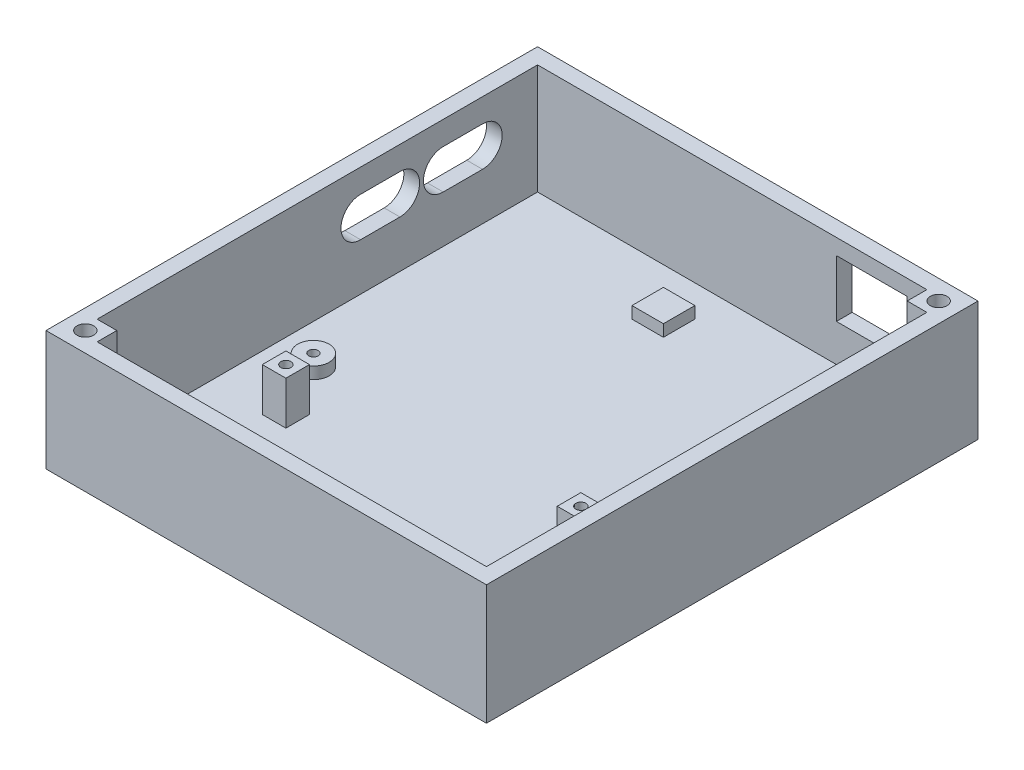
SolidWorks part; units mm, degrees
ref_plane "Front Plane" through (0, 0, 0) normal (0, 0, 1) x (1, 0, 0)
ref_plane "Top Plane" through (0, 0, 0) normal (0, 1, 0) x (1, 0, 0)
ref_plane "Right Plane" through (0, 0, 0) normal (1, 0, 0) x (0, 0, -1)
sketch "Sketch1" plane through (0, 0, 0) normal (0, 1, 0) x (1, 0, 0)
  line L1 (-56, -62.5) -> (56, -62.5)
  line L2 (-56, -62.5) -> (-56, 62.5)
  line L3 (-56, 62.5) -> (56, 62.5)
  line L4 (56, -62.5) -> (56, 62.5)
  line L5 (-56, -62.5) -> (56, 62.5) construction
  line L6 (-56, 62.5) -> (56, -62.5) construction
  point P0 (0, 0)
  dimension "D1" = 112
  dimension "D2" = 125
extrude "Boss-Extrude1" add sketch "Sketch1" along normal blind 2.5
sketch "Sketch2" plane through (0, 2.5, 0) normal (0, 1, 0) x (1, 0, 0)
  line L0 (-56, -62.5) -> (56, -62.5) construction
  line L1 (-12, 50.5) -> (-4, 50.5) construction
  line L2 (-12, 50.5) -> (-12, 42.5) construction
  line L3 (-12, 42.5) -> (-4, 42.5) construction
  line L4 (52, 53.5) -> (47, 53.5)
  line L5 (-4, 50.5) -> (-4, 42.5) construction
  line L6 (-56, 62.5) -> (-56, -62.5) construction
  line L7 (47, 53.5) -> (47, 58.5)
  line L8 (52, -58.5) -> (52, 58.5)
  line L9 (52, 58.5) -> (-52, 58.5)
  line L10 (-52, 58.5) -> (-52, -58.5)
  line L11 (-52, -58.5) -> (52, -58.5)
  line L12 (52, -58.5) -> (52, 53.5)
  line L13 (47, 58.5) -> (-52, 58.5)
  line L14 (-52, 58.5) -> (-52, -53.5)
  line L15 (-47, -58.5) -> (52, -58.5)
  line L16 (56, 62.5) -> (-56, 62.5) construction
  line L29 (-47, -58.5) -> (-47, -53.5)
  line L30 (-47, -53.5) -> (-52, -53.5)
  line L31 (56, -62.5) -> (56, 62.5) construction
  circle A0 centre (-42, -8.5) radius 1.2 construction
  circle A1 centre (38, -8.5) radius 1.2 construction
  circle A2 centre (-51, -57.5) radius 2.1
  circle A3 centre (51, 57.5) radius 2.1
  line M12 (56, -62.5) -> (56, 62.5)
  line M13 (56, 62.5) -> (-56, 62.5)
  line M14 (-56, 62.5) -> (-56, -62.5)
  line M15 (-56, -62.5) -> (56, -62.5)
  dimension "D1" = 2.4
  dimension "D13" = 4.2
  dimension "D15" = 4.2
  dimension "D18" = 5
  dimension "D2" = 80
  dimension "D3" = 5
  dimension "D5" = 8
  dimension "D6" = 62
  dimension "D7" = 5
  dimension "D8" = 14
  dimension "D9" = 8
  dimension "D10" = 8
  dimension "D11" = 40
  dimension "D12" = 5
  dimension "D14" = 5
  dimension "D16" = 5
  dimension "D17" = 5
  dimension "D4" = 4
extrude "Boss-Extrude2" add sketch "Sketch2" along normal blind 10 contours A0 | A1 | A3 A2 L29 L30 L14 L13 L7 L4 L12 L15 M15 M12 M13 M14 region at (48.9478, 2.5, -55.4478) region at (-48.9478, 2.5, 55.4478) region at (0, 2.5, 60.8216)
sketch "Sketch3" plane through (0, 2.5, 0) normal (0, 1, 0) x (1, 0, 0)
  line L0 (-32, -50.5) -> (-32, -25.5) construction
  line L1 (-35, -53.5) -> (40, -53.5) construction
  line L2 (-35, -53.5) -> (-35, -22.5) construction
  line L3 (-35, -22.5) -> (40, -22.5) construction
  line L4 (40, -53.5) -> (40, -22.5) construction
  line L5 (-32, -25.5) -> (37, -25.5) construction
  line L6 (37, -50.5) -> (37, -25.5) construction
  line L7 (-32, -50.5) -> (37, -50.5) construction
  line L8 (-38, -19.5) -> (43, -19.5)
  line L9 (43, -56.5) -> (43, -19.5)
  line L10 (-38, -56.5) -> (43, -56.5)
  line L11 (-38, -56.5) -> (-38, -19.5)
  line L12 (-47, -58.5) -> (52, -58.5) construction
  line L13 (-47, -58.5) -> (52, -58.5) construction
  line L14 (-32, -25.5) -> (-38, -25.5)
  line L15 (-32, -50.5) -> (-38, -50.5)
  line L16 (37, -25.5) -> (43, -25.5)
  line L17 (37, -50.5) -> (43, -50.5)
  line L18 (37, -25.5) -> (37, -19.5)
  line L19 (37, -50.5) -> (37, -56.5)
  line L20 (-32, -50.5) -> (-32, -56.5)
  line L21 (-32, -19.5) -> (-32, -25.5)
  circle A0 centre (-35, -22.5) radius 1.3
  circle A1 centre (40, -22.5) radius 1.3
  circle A2 centre (40, -53.5) radius 1.3
  circle A3 centre (-35, -53.5) radius 1.3
  point P17 (2.5, -22.5)
  point P19 (2.5, -58.5)
  dimension "D3" = 2.6
  dimension "D4" = 75
  dimension "D5" = 31
  dimension "D6" = 5
  dimension "D1" = 3
  dimension "D2" = 3
extrude "Boss-Extrude3" add sketch "Sketch3" along normal blind 11 contours L20 L15 L11 L10 A3 | L21 L8 L11 L14 A0 | L18 L16 L9 L8 A1 | L17 L19 L10 L9 A2 region at (-35, 2.5, 19.5849) region at (40, 2.5, 19.5849) region at (-35, 2.5, 50.5849) region at (42.9151, 2.5, 53.5)
sketch "Sketch5" plane through (0, 2.5, 0) normal (0, 1, 0) x (1, 0, 0)
  line L0 (-4, 50.5) -> (-4, 42.5) construction
  line L1 (-12, 50.5) -> (-4, 50.5) construction
  line L2 (-12, 50.5) -> (-12, 42.5) construction
  line L3 (-12, 42.5) -> (-4, 42.5) construction
  line L4 (-4, 50.5) -> (-4, 42.5)
  line L5 (-12, 50.5) -> (-4, 50.5)
  line L6 (-12, 50.5) -> (-12, 42.5)
  line L7 (-12, 42.5) -> (-4, 42.5)
  circle A0 centre (-42, -8.5) radius 4
  circle A1 centre (38, -8.5) radius 4
  circle A2 centre (38, -8.5) radius 1.2 construction
  circle A3 centre (38, -8.5) radius 1.2
  circle A4 centre (-42, -8.5) radius 1.2 construction
  circle A5 centre (-42, -8.5) radius 1.2
  dimension "D1" = 8
extrude "Boss-Extrude4" add sketch "Sketch5" along normal blind 3
sketch "Sketch6" plane through (0, 13.5, 0) normal (0, 1, 0) x (1, 0, 0)
  line L4 (-32, -56.5) -> (-32, -50.5)
  line L5 (-32, -50.5) -> (-38, -50.5)
  line L6 (-38, -50.5) -> (-38, -56.5)
  line L7 (-38, -56.5) -> (-32, -56.5)
  line L8 (-32, -56.5) -> (-32, -50.5)
  line L9 (-32, -50.5) -> (-38, -50.5)
  line L10 (-38, -50.5) -> (-38, -56.5)
  line L11 (-38, -56.5) -> (-32, -56.5)
  line L12 (37, -19.5) -> (37, -25.5)
  line L13 (37, -25.5) -> (43, -25.5)
  line L14 (43, -25.5) -> (43, -19.5)
  line L15 (43, -19.5) -> (37, -19.5)
  line L16 (37, -19.5) -> (37, -25.5)
  line L17 (37, -25.5) -> (43, -25.5)
  line L18 (43, -25.5) -> (43, -19.5)
  line L19 (43, -19.5) -> (37, -19.5)
  line L20 (43, -50.5) -> (37, -50.5)
  line L21 (37, -50.5) -> (37, -56.5)
  line L22 (37, -56.5) -> (43, -56.5)
  line L23 (43, -56.5) -> (43, -50.5)
  line L24 (43, -50.5) -> (37, -50.5)
  line L25 (37, -50.5) -> (37, -56.5)
  line L26 (37, -56.5) -> (43, -56.5)
  line L27 (43, -56.5) -> (43, -50.5)
  circle A0 centre (40, -53.5) radius 1.3 construction
  circle A1 centre (40, -22.5) radius 1.3
  circle A2 centre (40, -22.5) radius 1.3
  circle A3 centre (-35, -53.5) radius 1.3 construction
  circle A4 centre (40, -53.5) radius 1.3
  circle A5 centre (-35, -53.5) radius 1.3
  dimension "D1" = 0
  dimension "D2" = 0
  dimension "D3" = 0
  dimension "D4" = 0
extrude "Boss-Extrude5" add sketch "Sketch6" along normal blind 6.3
sketch "Sketch7" plane through (0, 12.5, 0) normal (0, 1, 0) x (1, 0, 0)
  line L4 (-56, -62.5) -> (56, -62.5)
  line L5 (56, -62.5) -> (56, 62.5)
  line L6 (56, 62.5) -> (-56, 62.5)
  line L7 (-56, 62.5) -> (-56, -62.5)
  line L8 (-56, -62.5) -> (56, -62.5)
  line L9 (56, -62.5) -> (56, 62.5)
  line L10 (56, 62.5) -> (-56, 62.5)
  line L11 (-56, 62.5) -> (-56, -62.5)
  circle M5 centre (51, 57.5) radius 2.1
  line M6 (47, 53.5) -> (52, 53.5)
  line M7 (52, 53.5) -> (52, -58.5)
  line M13 (52, 53.5) -> (52, -58.5)
  line M14 (52, -58.5) -> (-47, -58.5)
  line M15 (-47, -58.5) -> (-47, -53.5)
  line M16 (-47, -53.5) -> (-52, -53.5)
  line M17 (-52, -53.5) -> (-52, 58.5)
  line M18 (-52, 58.5) -> (47, 58.5)
  line M19 (47, 58.5) -> (47, 53.5)
  circle M22 centre (-51, -57.5) radius 2.1
  line M23 (-56, -62.5) -> (56, -62.5)
  line M24 (56, -62.5) -> (56, 62.5)
  line M25 (56, 62.5) -> (-56, 62.5)
  line M26 (-56, 62.5) -> (-56, -62.5)
  dimension "D1" = 0
extrude "Boss-Extrude6" add sketch "Sketch7" along normal blind 18 contours M26 M23 M24 M25 M22 M5 M7 M13 M14 M15 M16 M17 M18 M19 M6 region at (-54.3216, 12.5, 0)
sketch "Sketch9" plane through (-56, 0, 0) normal (-1, 0, 0) x (0, 0, 1)
  line L0 (-44.5, 19.5) -> (-34.5, 19.5) construction
  line L1 (-44.5, 24.5) -> (-34.5, 24.5)
  line L2 (-44.5, 14.5) -> (-34.5, 14.5)
  line L3 (-23.5, 19.5) -> (-13.5, 19.5) construction
  line L4 (-23.5, 24.5) -> (-13.5, 24.5)
  line L5 (-23.5, 14.5) -> (-13.5, 14.5)
  line L9 (-62.5, 30.5) -> (62.5, 30.5) construction
  line L10 (-62.5, 30.5) -> (-62.5, 0) construction
  arc A0 (-44.5, 24.5) -> (-44.5, 14.5) centre (-44.5, 19.5) ccw
  arc A1 (-34.5, 14.5) -> (-34.5, 24.5) centre (-34.5, 19.5) ccw
  arc A2 (-23.5, 24.5) -> (-23.5, 14.5) centre (-23.5, 19.5) ccw
  arc A3 (-13.5, 14.5) -> (-13.5, 24.5) centre (-13.5, 19.5) ccw
  point P2 (-39.5, 19.5)
  point P8 (-18.5, 19.5)
  point P23 (-29.5, 19.5)
  point P24 (-49.5, 19.5)
  dimension "D2" = 5
  dimension "D1" = 11
  dimension "D3" = 20
  dimension "D4" = 18
  dimension "D5" = 39
extrude "Cut-Extrude1" cut sketch "Sketch9" against normal up to next
sketch "Sketch10" plane through (0, 0, -62.5) normal (0, 0, -1) x (-1, 0, 0)
  line L3 (-24, 12) -> (-42, 12)
  line L5 (-56, 30.5) -> (-56, 0) construction
  line L6 (-42, 26.5) -> (-24, 26.5)
  line L7 (-42, 26.5) -> (-42, 12)
  line L8 (-24, 12) -> (-24, 26.5)
  line L9 (-56, 30.5) -> (56, 30.5) construction
  line L10 (-56, 0) -> (56, 0) construction
  point P8 (-33, 12)
  dimension "D1" = 14
  dimension "D2" = 23
  dimension "D3" = 18
  dimension "D4" = 4
  dimension "D5" = 12
extrude "Cut-Extrude2" cut sketch "Sketch10" against normal up to next
